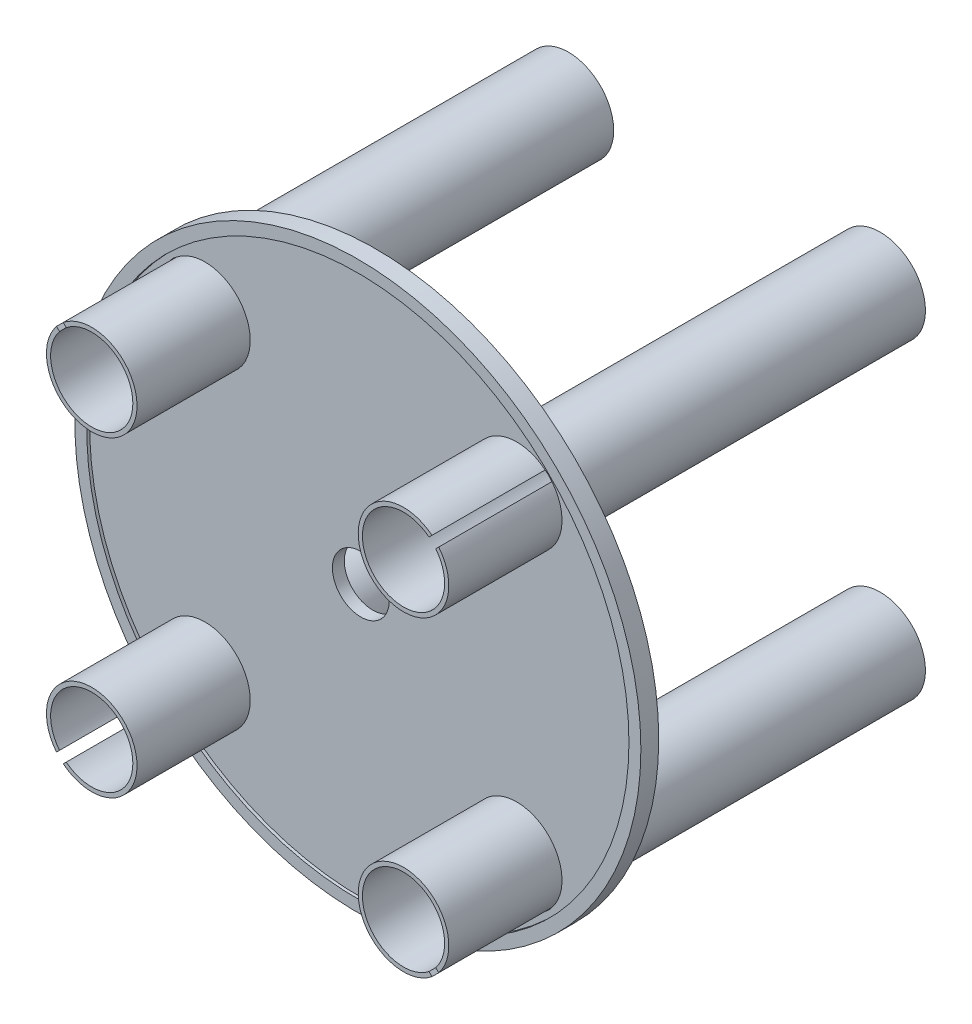
SolidWorks part; units mm, degrees
ref_plane "Front Plane" through (0, 0, 0) normal (0, 0, 1) x (1, 0, 0)
ref_plane "Top Plane" through (0, 0, 0) normal (0, 1, 0) x (1, 0, 0)
ref_plane "Right Plane" through (0, 0, 0) normal (1, 0, 0) x (0, 0, -1)
sketch "Sketch1" plane through (0, 0, 0) normal (0, 0, 1) x (1, 0, 0)
  line L0 (0, 87.6623) -> (0, -72.3453) construction
  line L1 (-133.8097, 0) -> (102.5349, 0) construction
  line L2 (0, 0) -> (-50.049, 50.049) construction
  circle A1 centre (0, 0) radius 45.5
  circle A2 centre (0, 0) radius 47.5
  circle A3 centre (0, 0) radius 4.7749
  circle A5 centre (-26.163, 26.163) radius 7.6
  circle A6 centre (-26.163, 26.163) radius 6.9
  circle A7 centre (26.163, 26.163) radius 6.9
  circle A8 centre (26.163, 26.163) radius 7.6
  circle A9 centre (26.163, -26.163) radius 6.9
  circle A10 centre (26.163, -26.163) radius 7.6
  circle A11 centre (-26.163, -26.163) radius 6.9
  circle A12 centre (-26.163, -26.163) radius 7.6
  arc A13 (-32.7689, 29.9209) -> (-29.8977, 32.782) centre (-26.163, 26.163) ccw
  arc A14 (-22.4088, 19.5549) -> (-19.5461, 22.4244) centre (-26.163, 26.163) ccw
  point P27 (0, 0)
  point P54 (-0.0706, 0.0708)
  point P55 (0, 45.7119)
  point P58 (0, 47.7261)
  point P72 (0, 0)
  point P383 (0, 0)
  dimension "D1" = 91
  dimension "D2" = 95
  dimension "D3" = 13.8
  dimension "D6" = 15.2
  dimension "D4" = 4
extrude "Boss-Extrude1" add sketch "Sketch1" along normal blind 1 and the other way blind 1 contours A1 A12 A10 A8 A5 A3 region at (-44.2131, 0, 0)
extrude "Boss-Extrude2" add sketch "Sketch1<3>" along normal blind 1.5 and the other way blind 1.5 contours A2 A1 region at (-46.1565, 0, 0)
sketch "Sketch1<3>" plane through (0, 0, 0) normal (0, 0, 1) x (1, 0, 0) same geometry as "Sketch1"
extrude "Boss-Extrude6" add sketch "Sketch1<6>" along normal blind 20 and the other way blind 60 contours A6 A5 A13 | A8 A7 | A10 A9 | A12 A11 region at (-19.0207, 24.2848, 0) region at (18.7779, 26.163, 0) region at (18.7779, -26.163, 0) region at (-33.548, -26.163, 0)
sketch "Sketch1<6>" plane through (0, 0, 0) normal (0, 0, 1) x (1, 0, 0) same geometry as "Sketch1"
ref_plane "Plane1" through (0, 0, 20) normal (0, 0, 1) x (1, 0, 0)
sketch "Sketch2" plane through (0, 0, 20) normal (0, 0, 1) x (1, 0, 0)
  line L0 (0, 0) -> (-35.6401, 35.6401)
  line L1 (-32.0738, 30.9402) -> (-31.5338, 30.4002)
  line L2 (-32.0738, 30.9402) -> (-31.5671, 31.5671)
  line L3 (-31.5338, 30.4002) -> (-30.4002, 31.5338)
  line L4 (-30.9402, 32.0738) -> (-31.5671, 31.5671)
  line L5 (-30.9402, 32.0738) -> (-30.4002, 31.5338)
  line L6 (32.0738, 30.9402) -> (31.5671, 31.5671)
  line L7 (30.9402, 32.0738) -> (31.5671, 31.5671)
  line L8 (30.9402, 32.0738) -> (30.4002, 31.5338)
  line L9 (30.4002, 31.5338) -> (31.5338, 30.4002)
  line L10 (32.0738, 30.9402) -> (31.5338, 30.4002)
  line L11 (30.9402, -32.0738) -> (31.5671, -31.5671)
  line L12 (32.0738, -30.9402) -> (31.5671, -31.5671)
  line L13 (32.0738, -30.9402) -> (31.5338, -30.4002)
  line L14 (31.5338, -30.4002) -> (30.4002, -31.5338)
  line L15 (30.9402, -32.0738) -> (30.4002, -31.5338)
  line L16 (-32.0738, -30.9402) -> (-31.5671, -31.5671)
  line L17 (-30.9402, -32.0738) -> (-31.5671, -31.5671)
  line L18 (-30.9402, -32.0738) -> (-30.4002, -31.5338)
  line L19 (-30.4002, -31.5338) -> (-31.5338, -30.4002)
  line L20 (-32.0738, -30.9402) -> (-31.5338, -30.4002)
  circle A0 centre (-26.163, 26.163) radius 7.6 construction
  point P11 (-30.967, 30.967)
  point P29 (0, 0)
  dimension "D1" = 4
extrude "Cut-Extrude1" cut sketch "Sketch2" against normal blind 20 contours L1 L3 L0 L2 | L5 L4 L0 L3 | L10 L6 L7 L8 L9 | L15 L11 L12 L13 L14 | L20 L16 L17 L18 L19 region at (-31.5307, 30.9739, 20) region at (-30.9739, 31.5307, 20) region at (31.2523, 31.2523, 20) region at (31.2523, -31.2523, 20) region at (-31.2523, -31.2523, 20)
